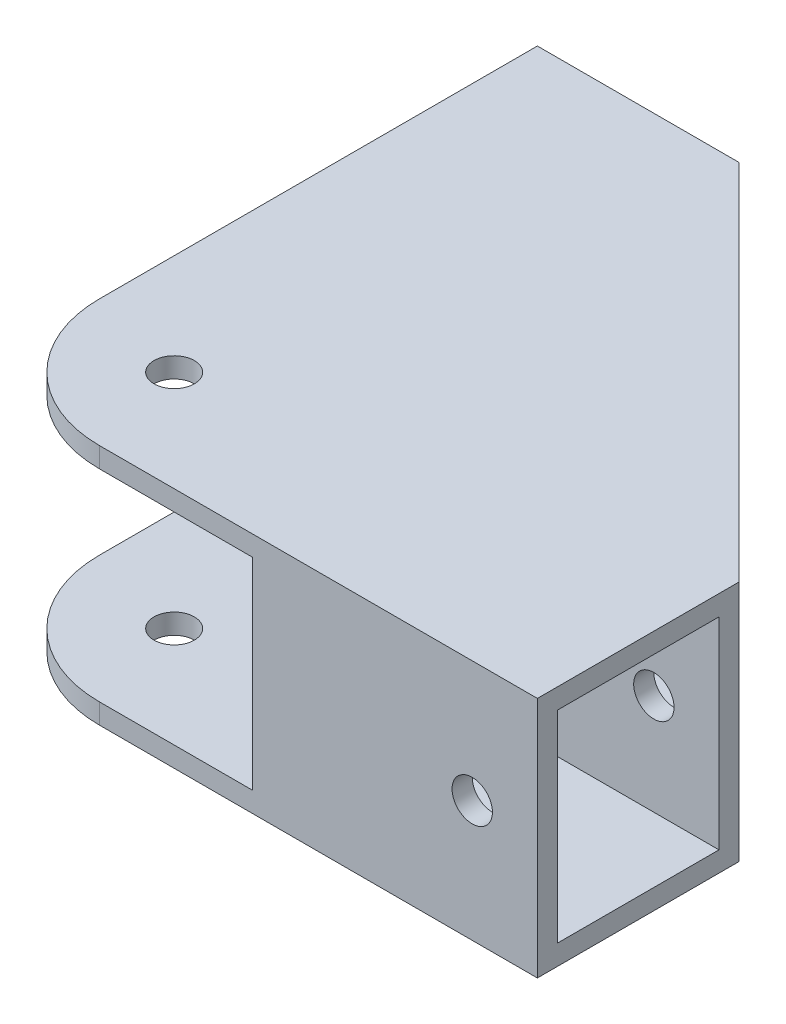
SolidWorks part; units mm, degrees
material "6061-T6 (SS)"
ref_plane "Front Plane" through (0, 0, 0) normal (0, 0, 1) x (1, 0, 0)
ref_plane "Top Plane" through (0, 0, 0) normal (0, 1, 0) x (1, 0, 0)
ref_plane "Right Plane" through (0, 0, 0) normal (1, 0, 0) x (0, 0, -1)
sketch "Sketch1" plane through (0, 0, 0) normal (0, 1, 0) x (1, 0, 0)
  line L0 (0, 0) -> (-88.9, 0)
  line L1 (-88.9, 0) -> (-88.9, 88.9)
  line L2 (-88.9, 88.9) -> (-57.15, 88.9)
  line L3 (-57.15, 88.9) -> (-57.15, 31.75)
  line L4 (-57.15, 31.75) -> (0, 31.75)
  line L5 (0, 31.75) -> (0, 0)
  point P6 (0, 88.9)
  dimension "D1" = 57.15
  dimension "D2" = 31.75
extrude "Boss-Extrude1" add sketch "Sketch1" along normal blind 38.1
sketch "Sketch2" plane through (0, 0, 0) normal (1, 0, 0) x (0, 0, -1)
  line L0 (31.75, 0) -> (0, 38.1) construction
  line L23 (3.175, 34.925) -> (3.175, 3.175)
  line L24 (3.175, 3.175) -> (28.575, 3.175)
  line L25 (28.575, 3.175) -> (28.575, 34.925)
  line L26 (28.575, 34.925) -> (3.175, 34.925)
  line L27 (3.175, 34.925) -> (3.175, 3.175)
  line L28 (3.175, 3.175) -> (28.575, 3.175)
  line L29 (28.575, 3.175) -> (28.575, 34.925)
  line L30 (28.575, 34.925) -> (3.175, 34.925)
  dimension "D1" = 3.175
extrude "Cut-Extrude1" cut sketch "Sketch2" against normal up to surface (88.9 mm away) up to face at (-88.9, 19.05, -44.45)
sketch "Sketch3" plane through (0, 0, -88.9) normal (0, 0, -1) x (-1, 0, 0)
  line L0 (57.15, 0) -> (88.9, 38.1) construction
  line L17 (60.325, 3.175) -> (85.725, 3.175)
  line L18 (60.325, 34.925) -> (60.325, 3.175)
  line L19 (85.725, 3.175) -> (85.725, 34.925)
  line L20 (85.725, 34.925) -> (60.325, 34.925)
  line L21 (60.325, 3.175) -> (85.725, 3.175)
  line L22 (60.325, 34.925) -> (60.325, 3.175)
  line L23 (85.725, 3.175) -> (85.725, 34.925)
  line L24 (85.725, 34.925) -> (60.325, 34.925)
  dimension "D1" = 3.175
extrude "Cut-Extrude2" cut sketch "Sketch3" against normal up to surface (88.9 mm away) up to face at (-44.45, 19.05, 0)
ref_plane "Plane1" through (0, 0, 0) normal (0.7071, 0, -0.7071) x (-0.7071, 0, -0.7071)
sketch "Sketch4" plane through (0, 0, 0) normal (0.7071, 0, -0.7071) x (-0.7071, 0, -0.7071)
  line L0 (125.7236, 38.1) -> (62.8618, 38.1) construction
  line L1 (100.3618, 34.925) -> (25.3618, 34.925)
  line L2 (100.3618, 34.925) -> (100.3618, 3.175)
  line L3 (100.3618, 3.175) -> (25.3618, 3.175)
  line L4 (25.3618, 34.925) -> (25.3618, 3.175)
  line L5 (100.3618, 34.925) -> (100.3618, 38.1) construction
  line L6 (100.3618, 3.175) -> (100.3618, 0) construction
  line L7 (125.7236, 0) -> (62.8618, 0) construction
  point P4 (62.8618, 34.925)
  dimension "D1" = 3.175
  dimension "D2" = 75
extrude "Cut-Extrude3" cut sketch "Sketch4" along normal blind 28.575 from vertex starting at point (-88.9, 38.1, 0)
fillet "Fillet4" radius 20 2 edges at (-88.9, 1.5875, 0) (-88.9, 36.5125, 0)
sketch "Sketch8" plane through (0, 34.925, 0) normal (0, -1, 0) x (1, 0, 0)
  line L0 (-73.025, -88.9) -> (-73.025, -0.43) construction
  line L1 (-57.15, -88.9) -> (-88.9, -88.9) construction
  line L2 (0, -15.875) -> (-88.47, -15.875) construction
  line L3 (0, 0) -> (0, -31.75) construction
  circle A0 centre (-73.025, -15.875) radius 3.175
  arc A2 (-68.9, 0) -> (-88.9, -20) centre (-68.9, -20) ccw construction
  point P13 (-73.025, -15.875)
  dimension "D1" = 6.35
extrude "Cut-Extrude8" cut sketch "Sketch8" against normal through all both and the other way through all
ref_plane "Plane2" through (-44.45, 0, -44.45) normal (0.7071, 0, 0.7071) x (0.7071, 0, -0.7071)
sketch "Sketch29" plane through (0, 38.1, 0) normal (0, 1, 0) x (1, 0, 0)
  line L0 (-57.15, 88.9) -> (0, 31.75)
  line L1 (-57.15, 88.9) -> (-57.15, 31.75)
  line L2 (-57.15, 31.75) -> (0, 31.75)
extrude "Boss-Extrude2" add sketch "Sketch29" against normal blind 3.175
sketch "Sketch35" plane through (-88.9, 0, 0) normal (-1, 0, 0) x (0, 0, 1)
  line L0 (-88.9, 38.1) -> (-88.9, 0) construction
  line L1 (-88.9, 38.1) -> (-20, 38.1) construction
  circle A0 centre (-78.65, 19.05) radius 3.175
  dimension "D1" = 10.25
  dimension "D3" = 6.35
  dimension "D2" = 19.05
extrude "Cut-Extrude10" cut sketch "Sketch35" against normal up to surface (31.75 mm away) up to face at (-57.15, 17.4625, -60.325)
sketch "Sketch36" plane through (0, 0, 0) normal (0, 0, 1) x (1, 0, 0)
  line L0 (0, 38.1) -> (0, 0) construction
  line L1 (-68.9, 38.1) -> (0, 38.1) construction
  circle A0 centre (-10.25, 19.05) radius 3.175
  dimension "D1" = 6.35
  dimension "D2" = 10.25
  dimension "D3" = 19.05
extrude "Cut-Extrude11" cut sketch "Sketch36" against normal up to surface (31.75 mm away) up to face at (-28.575, 17.4625, -31.75)
ref_plane "Plane5" through (0, 19.05, 0) normal (0, -1, 0) x (-1, 0, 0)
mirror "Mirror1" about plane through (0, 19.05, 0) normal (0, -1, 0) of "Boss-Extrude2"
fillet "Fillet8" radius 5 1 edges at (-60.325, 19.05, -28.575)
chamfer "Chamfer1" distance 10 angle 45 2 edges at (-51.6638, 19.05, -3.175) (-85.725, 19.05, -37.2362) first distance on face at (-7.075, 19.05, -3.175) first distance on face at (-85.725, 19.05, -75.475)
